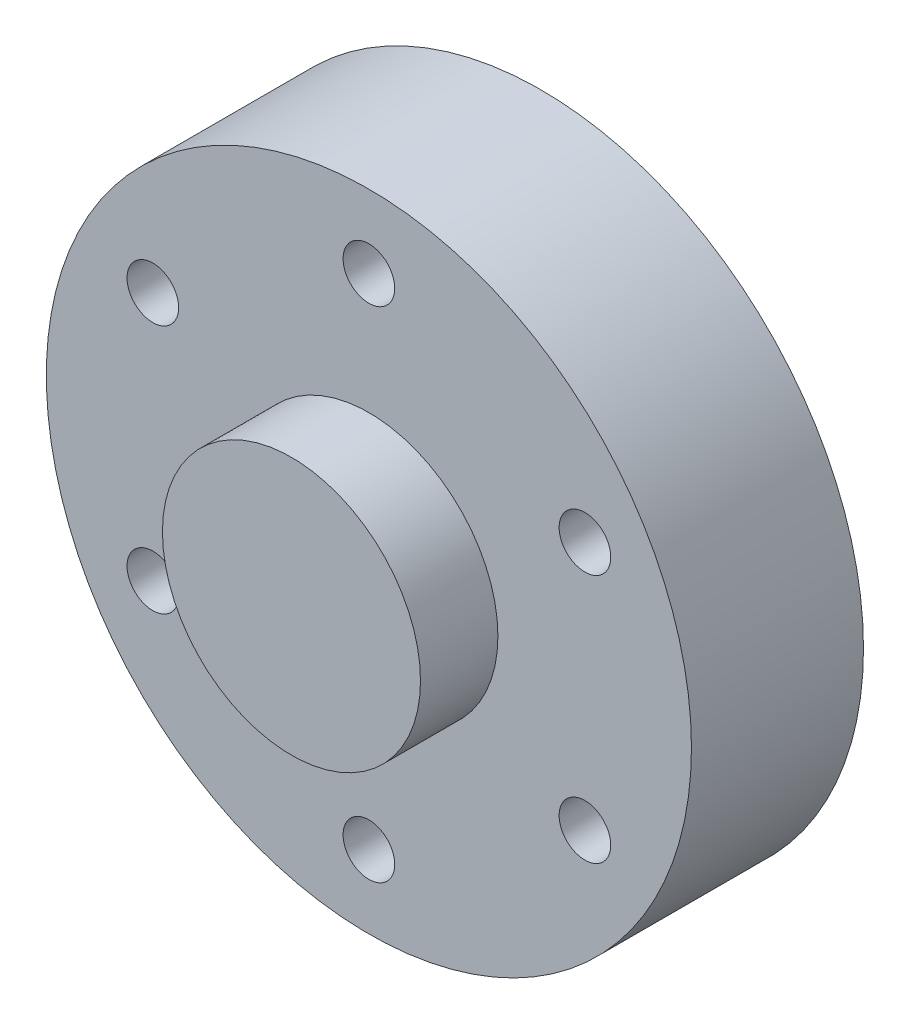
SolidWorks part; units mm, degrees
ref_plane "Front Plane" through (0, 0, 0) normal (0, 0, 1) x (1, 0, 0)
ref_plane "Top Plane" through (0, 0, 0) normal (0, 1, 0) x (1, 0, 0)
ref_plane "Right Plane" through (0, 0, 0) normal (1, 0, 0) x (0, 0, -1)
sketch "Sketch2" plane through (0, 0, 0) normal (0, 0, 1) x (1, 0, 0)
  circle A0 centre (0, 0) radius 9.5
  circle A1 centre (0, 0) radius 14.5 construction
  circle A3 centre (0, 0) radius 18.75
  circle A4 centre (0, 14.5) radius 1.5
  circle A5 centre (12.5574, 7.25) radius 1.5
  circle A6 centre (12.5574, -7.25) radius 1.5
  circle A7 centre (0, -14.5) radius 1.5
  circle A8 centre (-12.5574, -7.25) radius 1.5
  circle A9 centre (-12.5574, 7.25) radius 1.5
  point P21 (0, 0)
  dimension "D1" = 19
  dimension "D3" = 29
  dimension "D4" = 37.5
  dimension "D5" = 3
  dimension "D6" = 6
extrude "Boss-Extrude1" add sketch "Sketch2" along normal blind 10 contours A3 A9 A8 A7 A6 A5 A4 A0 | A0 region at (0, 0, 0) region at (-18.2197, 0, 0)
sketch "Sketch3" plane through (0, 0, 10) normal (0, 0, 1) x (1, 0, 0)
  circle A0 centre (0, 0) radius 7.5
  dimension "D1" = 15
extrude "Boss-Extrude2" add sketch "Sketch3" along normal blind 4.5
sketch "Sketch6" plane through (0, 0, 0) normal (0, 0, -1) x (-1, 0, 0)
  circle A0 centre (0, 0) radius 7.5
  dimension "D1" = 15
extrude "Boss-Extrude4" add sketch "Sketch6" along normal blind 4.5 contours A0
sketch "Sketch7" plane through (0, 0, -4.5) normal (0, 0, -1) x (-1, 0, 0)
  circle A0 centre (0, 0) radius 2
  dimension "D1" = 4
extrude "Boss-Extrude5" add sketch "Sketch7" along normal blind 1
fillet "Fillet2" radius 0.05 1 edges at (-2, 0, -5.5)
sketch "Sketch9" plane through (0, 0, -5.5) normal (0, 0, -1) x (-1, 0, 0)
  line L1 (-1.2247, 1.25) -> (1.2247, 1.25)
  arc A0 (-1.2247, 1.25) -> (1.2247, 1.25) centre (0, 0) ccw
  circle A1 centre (0, -0.25) radius 1.5 construction
  dimension "D1" = 3.5
  dimension "D2" = 3
extrude "Cut-Extrude1" cut sketch "Sketch9" against normal blind 11
